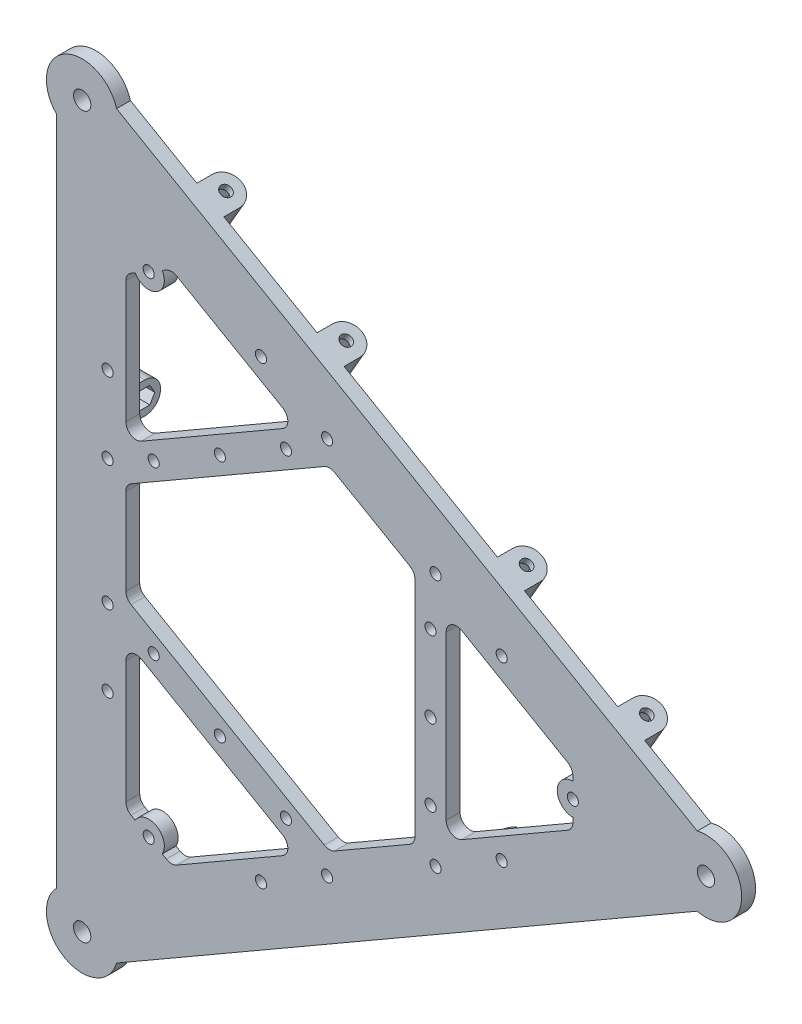
SolidWorks part; units mm, degrees
material "ABS"
ref_plane "前视基准面" through (0, 0, 0) normal (0, 0, 1) x (1, 0, 0)
ref_plane "上视基准面" through (0, 0, 0) normal (0, 1, 0) x (1, 0, 0)
ref_plane "右视基准面" through (0, 0, 0) normal (1, 0, 0) x (0, 0, -1)
sketch "草图1" plane through (0, 0, 0) normal (0, 0, 1) x (1, 0, 0)
  line L0 (0, 0) -> (-67.3124, 0) construction
  line L1 (134.6248, 0) -> (-67.3124, 116.5885)
  line L2 (-67.3124, 116.5885) -> (-67.3124, -116.5885)
  line L3 (-67.3124, -116.5885) -> (134.6248, 0)
  line L4 (-67.3124, 116.5885) -> (-67.3124, 85.5885) construction
  line L5 (-67.3124, 85.5885) -> (-67.3124, 45.5885) construction
  line L6 (0, 0) -> (117.3042, 0) construction
  line L7 (117.3042, 10) -> (117.3042, -10)
  line L8 (-49.9919, -106.5885) -> (-67.3124, -96.5885)
  line L9 (-58.6521, -101.5885) -> (-67.3124, -116.5885) construction
  line L10 (0, 0) -> (-58.6521, -101.5885) construction
  line L11 (-67.3124, 96.5885) -> (-49.9919, 106.5885)
  line L12 (85.9645, 5) -> (-38.6521, 76.9474)
  line L13 (-47.3124, 71.9474) -> (-47.3124, -71.9474)
  line L14 (-38.6521, -76.9474) -> (85.9645, -5)
  line L15 (85.9645, 5) -> (85.9645, -5)
  line L16 (-38.6521, -76.9474) -> (-47.3124, -71.9474)
  line L17 (-47.3124, 71.9474) -> (-38.6521, 76.9474)
  line L18 (94.6248, 0) -> (-47.3124, 81.9474) construction
  line L19 (-47.3124, 81.9474) -> (-47.3124, -81.9474) construction
  line L20 (-47.3124, -81.9474) -> (94.6248, 0) construction
  line L24 (117.3042, 0) -> (134.6248, 0) construction
  line L25 (-58.6521, 101.5885) -> (-67.3124, 116.5885) construction
  line L26 (0, 0) -> (-58.6521, 101.5885) construction
  line L27 (60.9645, -25.5) -> (60.9645, 25.5) construction
  line L28 (60.9645, 0) -> (40.4645, 0) construction
  line L29 (81.4645, 4.5) -> (81.4645, 7.5981)
  line L30 (81.4645, -4.5) -> (81.4645, -7.5981)
  line L31 (35.9645, 33.8675) -> (35.9645, -33.8675)
  line L32 (44.9645, 28.6714) -> (44.9645, -28.6714)
  line L33 (11.3479, -48.0799) -> (-47.3124, -14.2124)
  line L34 (2.3479, -53.2761) -> (-47.3124, -24.6047)
  line L35 (-52.5659, -40.0468) -> (-8.3986, -65.5468) construction
  line L36 (-44.6294, -68.3003) -> (-47.3124, -66.7513)
  line L37 (-36.8351, -72.8003) -> (-34.1521, -74.3494)
  line L38 (-47.3124, 14.2124) -> (11.3479, 48.0799)
  line L39 (-47.3124, 24.6047) -> (2.3479, 53.2761)
  line L40 (-8.3986, 65.5468) -> (-52.5659, 40.0468) construction
  line L41 (-36.8351, 72.8003) -> (-34.1521, 74.3494)
  line L42 (-44.6294, 68.3003) -> (-47.3124, 66.7513)
  line L43 (40.4645, 22) -> (40.4645, -22) construction
  line L44 (60.9645, 25.5) -> (41.9119, 36.5) construction
  line L45 (-8.3986, -65.5468) -> (10.654, -54.5468) construction
  line L46 (-1.1797, -46.0433) -> (-39.2848, -24.0433) construction
  line L47 (-52.5659, 40.0468) -> (-52.5659, 18.0468) construction
  line L48 (-39.2848, 24.0433) -> (-1.1797, 46.0433) construction
  circle A0 centre (0, 0) radius 67.3124 construction
  circle A1 centre (-59.9021, 103.7535) radius 2.5
  circle A2 centre (-59.9021, 103.7535) radius 10.3078
  circle A3 centre (119.8042, 0) radius 10.3078
  circle A4 centre (119.8042, 0) radius 2.5
  circle A5 centre (-59.9021, -103.7535) radius 10.3078
  circle A6 centre (-59.9021, -103.7535) radius 2.5
  circle A7 centre (40.4645, 0) radius 1.6
  circle A8 centre (60.9645, 25.5) radius 1.6
  circle A9 centre (81.4645, 0) radius 1.6
  circle A10 centre (81.4645, 0) radius 4.5
  circle A11 centre (60.9645, -25.5) radius 1.6
  circle A12 centre (-20.2323, -35.0433) radius 1.6
  circle A13 centre (-8.3986, -65.5468) radius 1.6
  circle A14 centre (-52.5659, -40.0468) radius 1.6
  circle A15 centre (-40.7323, -70.5503) radius 4.5
  circle A16 centre (-40.7323, -70.5503) radius 1.6
  circle A17 centre (-20.2323, 35.0433) radius 1.6
  circle A18 centre (-52.5659, 40.0468) radius 1.6
  circle A19 centre (-8.3986, 65.5468) radius 1.6
  circle A20 centre (-40.7323, 70.5503) radius 4.5
  circle A21 centre (-40.7323, 70.5503) radius 1.6
  circle A22 centre (40.4645, -22) radius 1.6
  circle A23 centre (40.4645, 22) radius 1.6
  circle A24 centre (41.9119, 36.5) radius 1.6
  circle A25 centre (41.9119, -36.5) radius 1.6
  circle A26 centre (-52.5659, -18.0468) radius 1.6
  circle A27 centre (10.654, -54.5468) radius 1.6
  circle A28 centre (-39.2848, -24.0433) radius 1.6
  circle A29 centre (-1.1797, -46.0433) radius 1.6
  circle A30 centre (10.654, 54.5468) radius 1.6
  circle A31 centre (-52.5659, 18.0468) radius 1.6
  circle A32 centre (-1.1797, 46.0433) radius 1.6
  circle A33 centre (-39.2848, 24.0433) radius 1.6
  point P13 (117.3042, 0)
  point P21 (0, 0)
  point P26 (85.9645, 0)
  point P33 (0, 0)
  point P36 (0, 0)
  point P45 (0, 0)
  point P98 (0, 0)
  point P126 (0, 0)
  dimension "D9" = 5
  dimension "D10" = 20.6155
  dimension "D14" = 3.2
  dimension "D15" = 9
  dimension "D19" = 22
  dimension "D1" = 233.1769
  dimension "D2" = 31
  dimension "D3" = 40
  dimension "D4" = 20
  dimension "D7" = 10
  dimension "D5" = 3
  dimension "D12" = 25.5
  dimension "D13" = 20.5
  dimension "D16" = 4.5
  dimension "D17" = 4.5
  dimension "D20" = 22
  dimension "D6" = 20
  dimension "D8" = 3
  dimension "D11" = 3
  dimension "D18" = 3
  dimension "D21" = 3
ref_plane "基准面4" through (-67.3124, 0, 0) normal (1, 0, 0) x (0, 0, -1)
sketch "草图2" plane through (-67.3124, 0, 0) normal (1, 0, 0) x (0, 0, -1)
  line L0 (0, 0) -> (4.5, 0) construction
  line L1 (0, 5) -> (0, -5) construction
  line L2 (4.5, 0) -> (4.5, 30) construction
  line L3 (4.5, 30) -> (4.5, 70) construction
  line L4 (4.5, 74.5) -> (0, 74.5)
  line L5 (0, 116.5885) -> (0, 85.5885) construction
  line L6 (4.5, 65.5) -> (0, 65.5)
  line L7 (0, 85.5885) -> (0, 45.5885) construction
  line L8 (4.5, 34.5) -> (0, 34.5)
  line L9 (4.5, 25.5) -> (0, 25.5)
  line L10 (0, 71.9474) -> (0, -71.9474) construction
  line L11 (0, 0) -> (18.2138, 0) construction
  line L12 (4.5, -30) -> (4.5, -70) construction
  line L13 (4.5, -25.5) -> (0, -25.5)
  line L14 (4.5, -34.5) -> (0, -34.5)
  line L15 (4.5, -65.5) -> (0, -65.5)
  line L16 (4.5, -74.5) -> (0, -74.5)
  line L17 (0, 0) -> (0, -74.5)
  line L18 (0, 0) -> (0, 74.5)
  circle A0 centre (4.5, 70) radius 4.5
  circle A1 centre (4.5, 30) radius 4.5
  circle A2 centre (4.5, 70) radius 1.6
  circle A3 centre (4.5, 30) radius 1.6
  circle A4 centre (4.5, -30) radius 1.6
  circle A5 centre (4.5, -70) radius 1.6
  circle A6 centre (4.5, -30) radius 4.5
  circle A7 centre (4.5, -70) radius 4.5
  dimension "D4" = 9
  dimension "D5" = 3.2
  dimension "D1" = 4.5
  dimension "D2" = 30
  dimension "D3" = 40
extrude "凸台-拉伸1" add sketch "草图1" along normal blind 4 contours L2 L3 L7 L1 L13 L17 L12 L15 L14 L16 | L1 A2 L2 L11 A1 | L2 A2 | L11 A2 | L1 A2 | L8 A6 L2 A5 L3 | L3 A5 | L2 A5 | L8 A5 | L7 A4 L3 A3 L1 | L7 A3 | L1 A3 | L3 A3 | L39 L13 L38 L12 A17 | A20 L41 L12 L17 | A20 L17 L13 L42 | A20 A21 | L32 L12 L31 L14 A7 | A10 L15 L12 L29 | A10 A9 | A10 L30 L14 L15 | L34 L14 L33 L13 A12 | A15 L36 L13 L16 | A15 A16 | A15 L16 L14 L37 region at (106.6764, 0, 0) region at (124.0965, 7.4344, 0) region at (122.7898, 0, 0) region at (114.0506, 0, 0) region at (-61.3949, 106.3391, 0) region at (-57.0253, 98.7707, 0) region at (-55.6099, 111.1879, 0) region at (124.0965, -7.4344, 0) region at (-55.6099, -111.1879, 0) region at (-61.3949, -106.3391, 0) region at (-57.0253, -98.7707, 0) region at (-68.4866, 103.7535, 0) region at (-68.4866, -103.7535, 0) region at (83.7969, 4.836, 0) region at (84.5565, -3.092, 0) region at (83.7969, -4.836, 0) region at (44.2812, 0, 0) region at (-18.3346, 31.7565, 0) region at (6.4955, -50.0677, 0) region at (-37.7104, 74.9882, 0) region at (-36.5085, 71.6821, 0) region at (-46.0865, 70.1523, 0) region at (-37.7104, -74.9882, 0) region at (-46.0865, -70.1523, 0) region at (-39.6005, -74.7741, 0)
extrude "凸台-拉伸2" add sketch "草图2" along normal blind 8 contours A0 A2 | A0 L18 L6 | A0 L4 L18 | L16 A7 L17 | A7 A5 | L17 A7 L15 region at (-67.3124, 73.4948, -1.0052) region at (-67.3124, -66.5052, -1.0052) region at (-67.3124, 73.092, -7.592) region at (-67.3124, 66.5052, -1.0052) region at (-67.3124, -66.908, -7.592) region at (-67.3124, -73.4948, -1.0052)
extrude "凸台-拉伸3" add sketch "草图2<4>" along normal blind 17 contours A1 A3 | A1 L18 L9 | A1 L8 L18 | L14 A6 L17 | A6 A4 | L17 A6 L13 region at (-67.3124, -26.5052, -1.0052) region at (-67.3124, 33.4948, -1.0052) region at (-67.3124, 33.092, -7.592) region at (-67.3124, 26.5052, -1.0052) region at (-67.3124, -26.908, -7.592) region at (-67.3124, -33.4948, -1.0052)
sketch "草图2<4>" plane through (-67.3124, 0, 0) normal (1, 0, 0) x (0, 0, -1) same geometry as "草图2"
sketch3d "3D草图3"
  line L0 (0, 0, 0) -> (0, 0, -186.0312)
sketch "草图4" plane through (-47.3124, 0, 0) normal (1, 0, 0) x (0, 0, -1)
  line L0 (1.671, 70) -> (3.0855, 67.55)
  line L1 (7.329, 70) -> (5.9145, 72.45)
  line L2 (5.9145, 72.45) -> (3.0855, 72.45)
  line L3 (3.0855, 72.45) -> (1.671, 70)
  line L4 (3.0855, 67.55) -> (5.9145, 67.55)
  line L5 (5.9145, 67.55) -> (7.329, 70)
  line L6 (4.5, 70) -> (7.329, 70) construction
  line L7 (7.329, 30) -> (5.9145, 32.45)
  line L8 (5.9145, 32.45) -> (3.0855, 32.45)
  line L9 (3.0855, 32.45) -> (1.671, 30)
  line L10 (1.671, 30) -> (3.0855, 27.55)
  line L11 (3.0855, 27.55) -> (5.9145, 27.55)
  line L12 (5.9145, 27.55) -> (7.329, 30)
  line L13 (7.329, -30) -> (5.9145, -27.55)
  line L14 (5.9145, -27.55) -> (3.0855, -27.55)
  line L15 (3.0855, -27.55) -> (1.671, -30)
  line L16 (1.671, -30) -> (3.0855, -32.45)
  line L17 (3.0855, -32.45) -> (5.9145, -32.45)
  line L18 (5.9145, -32.45) -> (7.329, -30)
  line L19 (7.329, -70) -> (5.9145, -67.55)
  line L20 (5.9145, -67.55) -> (3.0855, -67.55)
  line L21 (3.0855, -67.55) -> (1.671, -70)
  line L22 (1.671, -70) -> (3.0855, -72.45)
  line L23 (3.0855, -72.45) -> (5.9145, -72.45)
  line L24 (5.9145, -72.45) -> (7.329, -70)
  line L25 (4.5, 30) -> (7.329, 30) construction
  line L26 (4.5, -30) -> (7.329, -30) construction
  line L27 (4.5, -70) -> (7.329, -70) construction
  circle A0 centre (4.5, 70) radius 2.45 construction
  circle A1 centre (4.5, 30) radius 2.45 construction
  circle A2 centre (4.5, -30) radius 2.45 construction
  circle A3 centre (4.5, -70) radius 2.45 construction
  point P28 (4.5, -72.45)
  dimension "D1" = 4.9
  dimension "D2" = 4.9
  dimension "D3" = 4.9
  dimension "D4" = 4.9
extrude "切除-拉伸1" cut sketch "草图4" against normal blind 18
pattern_circular "阵列(圆周)1" count 3 over 360 about axis through (0, 0, 0) along (0, 0, -1) of "凸台-拉伸3"
pattern_circular "阵列(圆周)2" count 3 over 360 about axis through (0, 0, 0) along (0, 0, -1) of "凸台-拉伸2"
pattern_circular "阵列(圆周)3" count 3 over 360 about axis through (0, 0, 0) along (0, 0, -1) of "切除-拉伸1"
fillet "圆角1" radius 3 18 edges at (35.9645, -33.8675, 2) (11.3479, -48.0799, 2) (-47.3124, -14.2124, 2) (-47.3124, 14.2124, 2) (35.9645, 33.8675, 2) (11.3479, 48.0799, 2) (-47.3124, -24.6047, 2) (-47.3124, -66.7513, 2) (-34.1521, -74.3494, 2) (2.3479, -53.2761, 2) (44.9645, -28.6714, 2) (81.4645, -7.5981, 2) (81.4645, 7.5981, 2) (44.9645, 28.6714, 2) (-34.1521, 74.3494, 2) (-47.3124, 66.7513, 2) (-47.3124, 24.6047, 2) (2.3479, 53.2761, 2)
